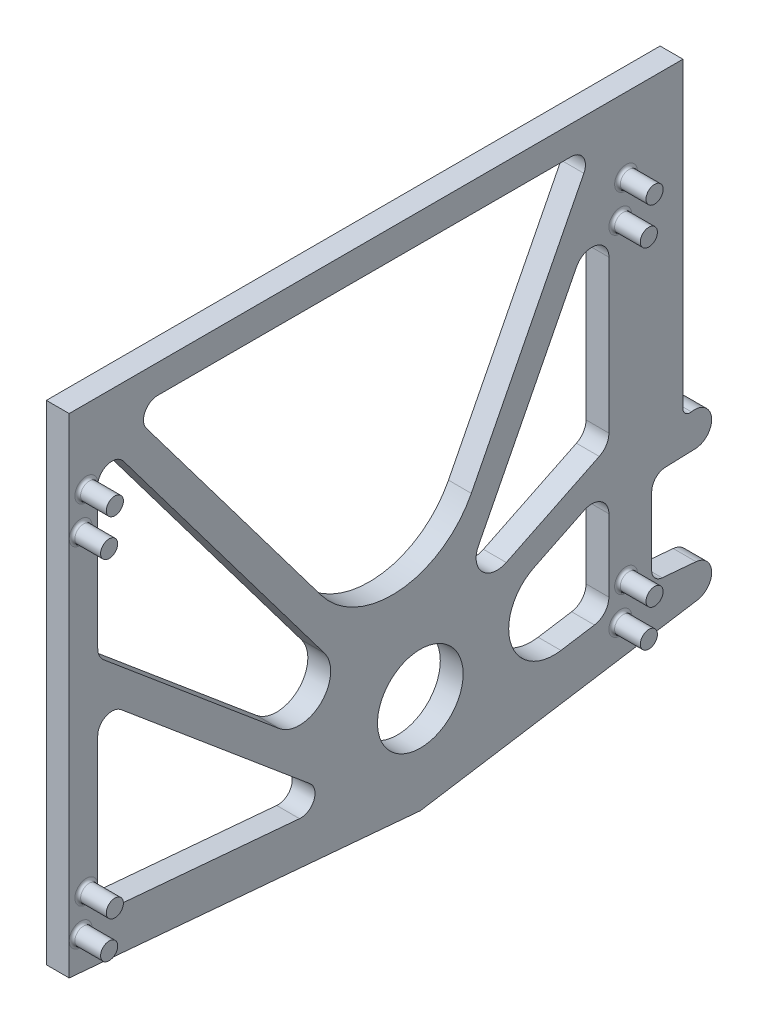
SolidWorks part; units mm, degrees
material "1023 Carbon Steel Sheet (SS)"
ref_plane "Спереди" through (0, 0, 0) normal (0, 0, 1) x (1, 0, 0)
ref_plane "Сверху" through (0, 0, 0) normal (0, 1, 0) x (1, 0, 0)
ref_plane "Справа" through (0, 0, 0) normal (1, 0, 0) x (0, 0, -1)
other "Configuration Table"
sketch "Sketch2" plane through (0, 0, 0) normal (1, 0, 0) x (0, 0, -1)
  line L0 (-769.0851, 14.2159) -> (1403.3589, 14.2159) construction
  line L1 (0, -34) -> (-123, -23.2389)
  line L2 (-123, 148) -> (92, 148)
  line L3 (-123, 148) -> (-123, -23.2389)
  line L6 (0, -34) -> (97, -18.6367)
  line L7 (0, 9.7878) -> (0, -76.711) construction
  line L8 (-113, -3.5585) -> (-113, 45.221)
  line L9 (-104.7861, 49.0512) -> (-38.667, -6.4293)
  line L10 (-42.3167, -15.2405) -> (-107.5229, -9.5357)
  line L11 (-113, 71.7954) -> (-113, 121.0542)
  line L14 (-91.9591, 138) -> (52.8427, 138)
  line L15 (57.2977, 130.73) -> (17.8728, 53.3544)
  line L16 (-34.7343, 48.7519) -> (-95.9523, 129.9909)
  line L17 (-104.0068, 124.0632) -> (-33.6119, 30.646)
  line L18 (-49.4183, 15.6462) -> (-110.8567, 67.1992)
  line L19 (66.0614, 100.9111) -> (66.0614, 47.5378)
  line L20 (62.6916, 42.145) -> (30.1096, 26.2537)
  line L21 (20.3486, 36.1866) -> (54.7154, 103.635)
  line L22 (66.0614, 23.0605) -> (66.0614, -2.213)
  line L23 (61, -8.1391) -> (49.2707, -9.9968)
  line L24 (39.8509, 19.8788) -> (57.4312, 28.4533)
  line L25 (92, 148) -> (92, 42)
  line L26 (96.2701, 27.6483) -> (85.8875, 27.287)
  line L27 (81.0614, 22.29) -> (81.0614, -1.71)
  line L28 (84.7128, -5.6948) -> (96.5843, -6.7334)
  circle A0 centre (0, 0) radius 30 construction
  circle A1 centre (0, 0) radius 15
  arc A2 (17.8728, 53.3544) -> (-34.7343, 48.7519) centre (-9.8687, 67.4894) cw
  arc A3 (-33.6119, 30.646) -> (-49.4183, 15.6462) centre (-42.3696, 24.0466) cw
  arc A4 (30.1096, 26.2537) -> (20.3486, 36.1866) centre (26.8909, 32.8531) cw
  arc A5 (49.2707, -9.9968) -> (39.8509, 19.8788) centre (46.7933, 5.6449) cw
  arc A6 (-38.667, -6.4293) -> (-42.3167, -15.2405) centre (-41.8809, -10.2595) cw
  arc A7 (-113, 45.221) -> (-104.7861, 49.0512) centre (-108, 45.221) cw
  arc A8 (66.0614, 100.9111) -> (54.7154, 103.635) centre (60.0614, 100.9111) ccw
  arc A9 (-91.9591, 138) -> (-95.9523, 129.9909) centre (-91.9591, 133) ccw
  arc A10 (52.8427, 138) -> (57.2977, 130.73) centre (52.8427, 133) cw
  arc A11 (-113, 121.0542) -> (-104.0068, 124.0632) centre (-108, 121.0542) cw
  arc A12 (66.0614, 23.0605) -> (57.4312, 28.4533) centre (60.0614, 23.0605) ccw
  arc A13 (66.0614, 47.5378) -> (62.6916, 42.145) centre (60.0614, 47.5378) cw
  arc A14 (66.0614, -2.213) -> (61, -8.1391) centre (60.0614, -2.213) cw
  arc A15 (-113, 71.7954) -> (-110.8567, 67.1992) centre (-107, 71.7954) ccw
  arc A16 (-113, -3.5585) -> (-107.5229, -9.5357) centre (-107, -3.5585) ccw
  arc A17 (92, 42) -> (94.9592, 39.5425) centre (94.5, 42) ccw
  arc A18 (94.9592, 39.5425) -> (96.2701, 27.6483) centre (96.0614, 33.6446) cw
  arc A19 (85.8875, 27.287) -> (81.0614, 22.29) centre (86.0614, 22.29) ccw
  arc A20 (81.0614, -1.71) -> (84.7128, -5.6948) centre (85.0614, -1.71) ccw
  arc A21 (96.5843, -6.7334) -> (97, -18.6367) centre (96.0614, -12.7106) cw
  point P60 (-113, 55.9435)
  point P65 (-101.9876, 138)
  point P68 (61.0019, 138)
  point P71 (-113, 135.9976)
  point P74 (66.0614, 32.6625)
  point P77 (66.0614, 43.7886)
  point P80 (66.0614, -7.3375)
  point P83 (-113, 68.9976)
  point P86 (-113, -9.0565)
  dimension "D1" = 60
  dimension "D8" = 15
  dimension "D31" = 5
  dimension "D32" = 6
  dimension "D33" = 5
  dimension "D34" = 5
  dimension "D35" = 6
  dimension "D36" = 6
  dimension "D38" = 6
  dimension "D39" = 5
  dimension "D40" = 4
  dimension "D43" = 2.5
  dimension "D2" = 123
  dimension "D4" = 148
  dimension "D5" = 85
  dimension "D6" = 81
  dimension "D7" = 34
  dimension "D9" = 10
  dimension "D10" = 215
  dimension "D11" = 10
  dimension "D12" = 10
  dimension "D13" = 10
  dimension "D14" = 10
  dimension "D15" = 10
  dimension "D16" = 15
  dimension "D17" = 50
  dimension "D18" = 65
  dimension "D19" = 67
  dimension "D20" = 37
  dimension "D21" = 97
  dimension "D22" = 40
  dimension "D23" = 16
  dimension "D24" = 17
  dimension "D25" = 64
  dimension "D26" = 83
  dimension "D27" = 63
  dimension "D28" = 95
  dimension "D29" = 111.7508
  dimension "D30" = 40
  dimension "D37" = 106
  dimension "D41" = 24
  dimension "D42" = 21
  dimension "D44" = 15
extrude "Boss-Extrude1" add sketch "Sketch2" along normal blind 8
sketch "Sketch3" plane through (8, 0, 0) normal (1, 0, 0) x (0, 0, -1)
  line L0 (-118, 141.3117) -> (-118, -10.2599) construction
  line L1 (-113, 121.0542) -> (-113, 71.7954) construction
  line L2 (-123, 148) -> (-123, -23.2389) construction
  line L3 (71.0614, 134.6943) -> (71.0614, -7.1333) construction
  line L6 (66.0614, 47.5378) -> (66.0614, 100.9111) construction
  circle A0 centre (-117, 122) radius 3
  circle A1 centre (-119, 110) radius 3
  circle A2 centre (72.0614, 122) radius 3
  circle A3 centre (70.0614, 110) radius 3
  circle A4 centre (-117, 0) radius 3
  circle A5 centre (-119, -12) radius 3
  circle A6 centre (72.0614, 0) radius 3
  circle A7 centre (70.0614, -12) radius 3
  dimension "D1" = 6
  dimension "D2" = 1
  dimension "D3" = 1
  dimension "D4" = 12
  dimension "D5" = 110
  dimension "D6" = 1
  dimension "D7" = 1
  dimension "D8" = 12
  dimension "D9" = 1
  dimension "D10" = 1
  dimension "D11" = 5
extrude "Boss-Extrude2" add sketch "Sketch3" along normal blind 10
sketch "Sketch4" plane through (8, 0, 0) normal (1, 0, 0) x (0, 0, -1)
  circle A0 centre (0, 0) radius 30
  dimension "D1" = 60
fillet "Fillet1" radius 1 8 edges at (8, -12, -67.0614) (8, 0, -69.0614) (8, -12, 122) (8, 0, 120) (8, 110, -67.0614) (8, 122, -69.0614) (8, 110, 122) (8, 122, 120)
equation "\"D8@Sketch3\"=\"D4@Sketch3\""
